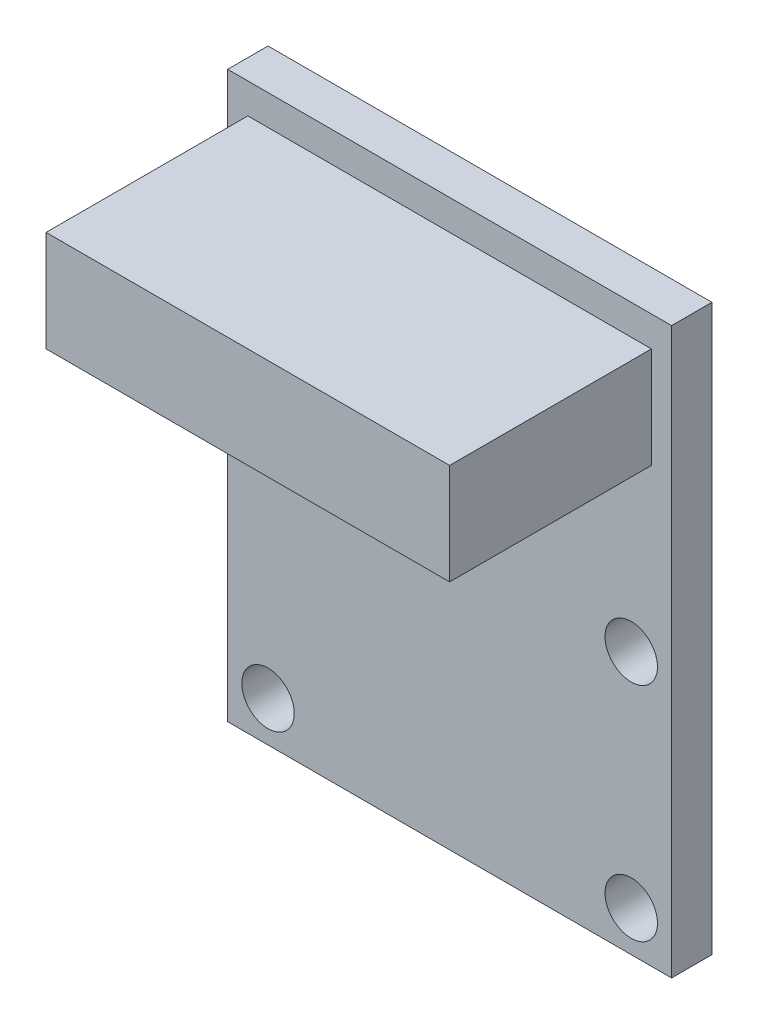
SolidWorks part; units mm, degrees
ref_plane "Front" through (0, 0, 0) normal (0, 0, 1) x (1, 0, 0)
ref_plane "Top" through (0, 0, 0) normal (0, 1, 0) x (1, 0, 0)
ref_plane "Right" through (0, 0, 0) normal (1, 0, 0) x (0, 0, -1)
sketch "草图1" plane through (0, 0, 0) normal (0, 0, 1) x (1, 0, 0)
  line L1 (-11, 14) -> (11, 14)
  line L2 (-11, 14) -> (-11, -14)
  line L3 (-11, -14) -> (11, -14)
  line L4 (11, 14) -> (11, -14)
  line L5 (0, -14) -> (0, 14) construction
  line L6 (-11, 0) -> (11, 0) construction
  line L7 (-9, -0.9979) -> (9, -0.9979) construction
  line L8 (-9, -0.9979) -> (-9, -11.9979) construction
  line L9 (-9, -11.9979) -> (9, -11.9979) construction
  line L10 (9, -0.9979) -> (9, -11.9979) construction
  line L11 (0, -11.9979) -> (0, -0.9979) construction
  line L12 (-9, -6.4979) -> (9, -6.4979) construction
  line L13 (-3, -9.4979) -> (3, -9.4979) construction
  line L14 (-3, -9.4979) -> (-3, -3.4979) construction
  line L15 (-3, -3.4979) -> (3, -3.4979) construction
  line L16 (3, -9.4979) -> (3, -3.4979) construction
  line L17 (-3, -9.4979) -> (3, -3.4979) construction
  line L18 (-3, -3.4979) -> (3, -9.4979) construction
  circle A0 centre (-9, -11.9979) radius 1.3
  circle A1 centre (-9, -0.9979) radius 1.3
  circle A2 centre (9, -0.9979) radius 1.3
  circle A3 centre (9, -11.9979) radius 1.3
  point P13 (0, -6.4979)
  point P70 (0, -6.4979)
  point P92 (0, 0)
  dimension "D5" = 2.6
  dimension "D6" = 2.6
  dimension "D7" = 2.6
  dimension "D8" = 2.6
  dimension "D1" = 22
  dimension "D2" = 28
  dimension "D3" = 11
  dimension "D4" = 18
  dimension "D9" = 0
  dimension "D10" = 0
extrude "凸台-拉伸1" add sketch "草图1" along normal blind 2
sketch "草图2" plane through (0, 0, 2) normal (0, 0, 1) x (1, 0, 0)
  line L0 (-11, 14) -> (-11, -14) construction
  line L1 (-10, 7.5) -> (10, 7.5)
  line L2 (-10, 7.5) -> (-10, 12.5)
  line L3 (-10, 12.5) -> (10, 12.5)
  line L4 (10, 7.5) -> (10, 12.5)
  line L5 (0, 12.5) -> (0, 0.078) construction
  line L6 (-10, 10) -> (10, 10) construction
  circle A0 centre (9, -0.9979) radius 1.3 construction
  point P96 (0, 10)
  dimension "D1" = 20
  dimension "D2" = 5
  dimension "D3" = 10
  dimension "D4" = 1
extrude "凸台-拉伸2" add sketch "草图2" along normal blind 10
